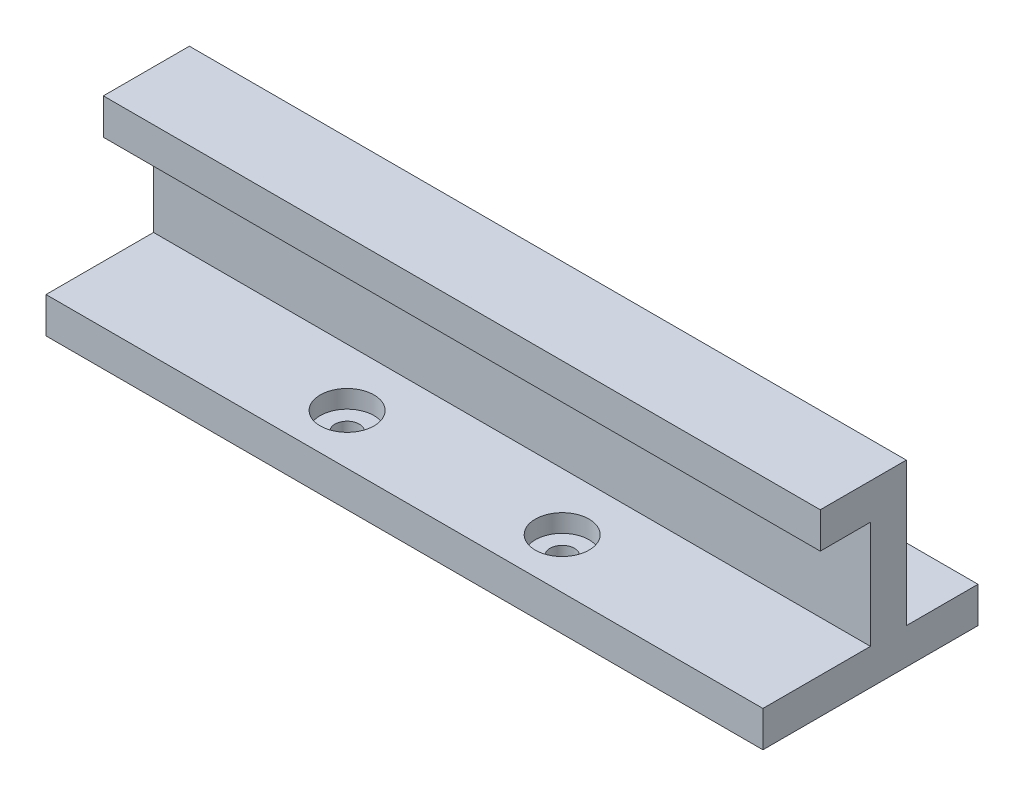
SolidWorks part; units mm, degrees
ref_plane "Front Plane" through (0, 0, 0) normal (0, 0, 1) x (1, 0, 0)
ref_plane "Top Plane" through (0, 0, 0) normal (0, 1, 0) x (1, 0, 0)
ref_plane "Right Plane" through (0, 0, 0) normal (1, 0, 0) x (0, 0, -1)
sketch "Sketch1" plane through (0, 0, 0) normal (0, 1, 0) x (1, 0, 0)
  line L0 (50, 20) -> (50, 0) construction
  line L1 (0, 0) -> (100, 0)
  line L2 (0, 0) -> (0, 20)
  line L3 (0, 20) -> (100, 20)
  line L4 (100, 0) -> (100, 20)
  circle A0 centre (35, 7) radius 1.7
  circle A1 centre (65, 7) radius 1.7
  dimension "D3" = 3.4
  dimension "D4" = 3.4
  dimension "D1" = 20
  dimension "D2" = 100
  dimension "D5" = 7
  dimension "D6" = 7
  dimension "D7" = 30
  dimension "D8" = 15
extrude "Extrude-Base" add sketch "Sketch1" along normal blind 5
sketch "Sketch2" plane through (0, 5, 0) normal (0, 1, 0) x (1, 0, 0)
  line L0 (100, 0) -> (100, 20) construction
  line L1 (0, 20) -> (100, 20)
  line L2 (0, 20) -> (0, 15)
  line L3 (0, 15) -> (100, 15)
  line L4 (100, 20) -> (100, 15)
  dimension "D1" = 5
extrude "Extrude-Vertical clamp" add sketch "Sketch2" along normal blind 20
sketch "Sketch3" plane through (0, 0, -15) normal (0, 0, 1) x (1, 0, 0)
  line L0 (100, 25) -> (100, 5) construction
  line L1 (0, 25) -> (100, 25)
  line L2 (0, 25) -> (0, 20)
  line L3 (0, 20) -> (100, 20)
  line L4 (100, 25) -> (100, 20)
  dimension "D1" = 5
extrude "Extrude-Clamp Roof" add sketch "Sketch3" along normal blind 7
sketch "Sketch5" plane through (0, 0, 0) normal (0, 1, 0) x (1, 0, 0)
  line L0 (100, 20) -> (100, 30)
  line L1 (100, 30) -> (0, 30)
  line L2 (0, 30) -> (0, 20)
  line L3 (0, 20) -> (100, 20)
  line L4 (50, 20) -> (50, 30) construction
  circle A0 centre (70, 25) radius 1.7
  circle A1 centre (30, 25) radius 1.7
  dimension "D6" = 3.4
  dimension "D7" = 3.4
  dimension "D1" = 10
  dimension "D2" = 20
  dimension "D3" = 20
  dimension "D4" = 5
  dimension "D5" = 5
extrude "Boss-Extrude4" add sketch "Sketch5" along normal blind 5
sketch "Sketch4" plane through (0, 5, 0) normal (0, 1, 0) x (1, 0, 0)
  circle A0 centre (35, 7) radius 3.75
  circle A1 centre (65, 7) radius 3.75
  circle A2 centre (35, 7) radius 1.7 construction
  circle A3 centre (65, 7) radius 1.7 construction
  circle A4 centre (30, 25) radius 3.75
  circle A5 centre (70, 25) radius 3.75
  dimension "D1" = 7.5
  dimension "D2" = 7.5
  dimension "D3" = 7.5
  dimension "D4" = 7.5
extrude "Cut-Extrude1" cut sketch "Sketch4" against normal blind 2.5
equation "\"screwInset\"=7.5"
equation "\"D1@Sketch4\"=\"screwInset\""
equation "\"D2@Sketch4\"=\"screwInset\""
equation "\"D3@Sketch4\"=\"screwInset\""
equation "\"D4@Sketch4\"=\"screwInset\""
equation "\"hole_bolt\"=3.4"
equation "\"D3@Sketch1\"=\"hole_bolt\""
equation "\"D4@Sketch1\"=\"hole_bolt\""
equation "\"D7@Sketch5\"=\"hole_bolt\""
equation "\"D6@Sketch5\"=\"hole_bolt\""
